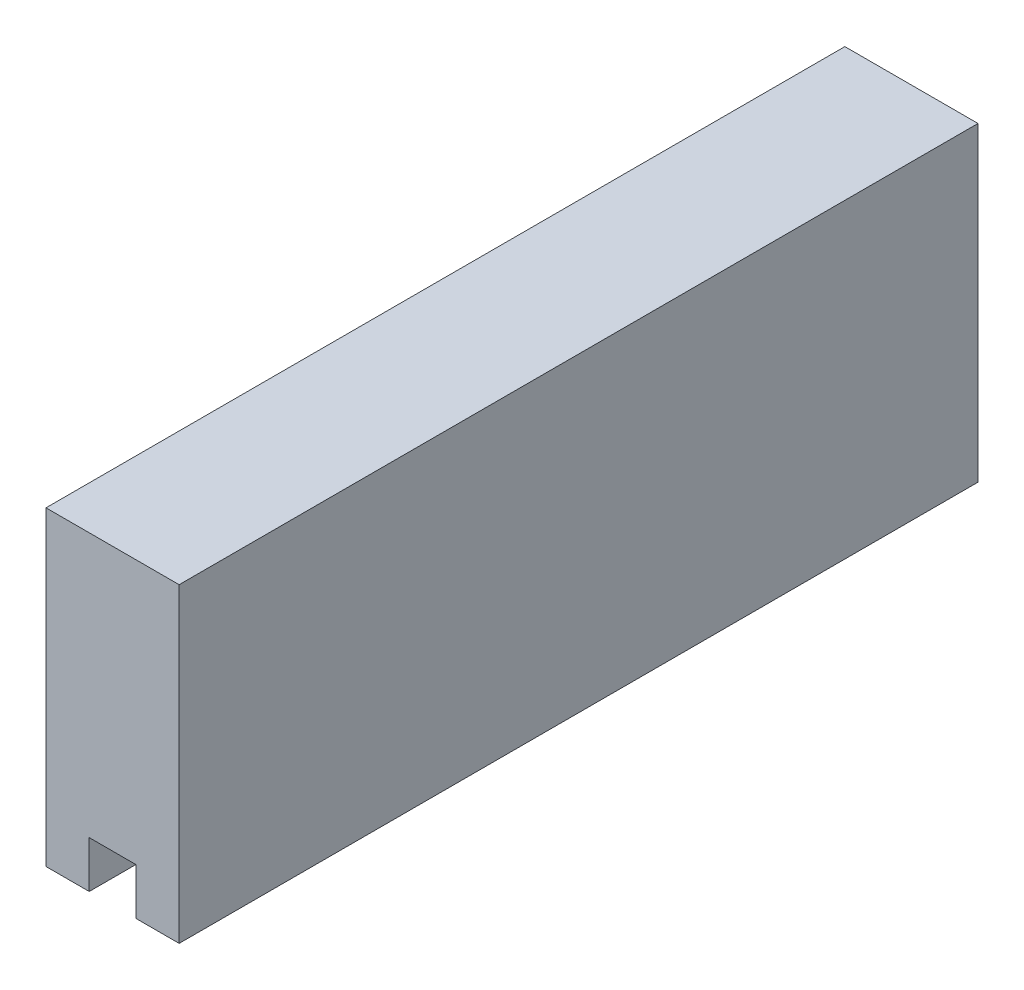
SolidWorks part; units mm, degrees
ref_plane "xy_plane" through (0, 0, 0) normal (0, 0, 1) x (1, 0, 0)
ref_plane "zx_plane" through (0, 0, 0) normal (0, 1, 0) x (1, 0, 0)
ref_plane "yz_plane" through (0, 0, 0) normal (1, 0, 0) x (0, 0, -1)
ref_axis "x_axis" through (-80.9, 0, 0) along (1, 0, 0)
ref_axis "y_axis" through (0, -50, 0) along (0, 1, 0)
ref_axis "z_axis" through (0, 0, -80.9) along (0, 0, 1)
ref_plane "xMid_plane" through (0, 0, 0) normal (1, 0, 0) x (0, 0, -1)
ref_plane "xMin_plane" through (-15, 0, 0) normal (1, 0, 0) x (0, 0, -1)
ref_plane "xMax_plane" through (15, 0, 0) normal (1, 0, 0) x (0, 0, -1)
ref_plane "yMid_plane" through (0, 0, 0) normal (0, 1, 0) x (1, 0, 0)
ref_plane "yMin_plane" through (0, -35, 0) normal (0, 1, 0) x (1, 0, 0)
ref_plane "yMax_plane" through (0, 35, 0) normal (0, 1, 0) x (1, 0, 0)
ref_plane "zMid_plane" through (0, 0, 0) normal (0, 0, 1) x (1, 0, 0)
ref_plane "zMin_plane" through (0, 0, -90) normal (0, 0, 1) x (1, 0, 0)
ref_plane "zMax_plane" through (0, 0, 90) normal (0, 0, 1) x (1, 0, 0)
sketch "projectionXy_sketch" plane through (0, 0, 0) normal (0, 0, 1) x (1, 0, 0)
  line L0 (55, 35) -> (-55, 35) construction
  line L1 (-15, 35) -> (15, 35)
  line L2 (-15, 35) -> (-15, -35)
  line L3 (-15, -35) -> (15, -35)
  line L4 (15, 35) -> (15, -35)
  line L5 (55, -35) -> (-55, -35) construction
  line L6 (15, -55) -> (15, 55) construction
  line L7 (-15, -55) -> (-15, 55) construction
extrude "mainBody_extrude" add sketch "projectionXy_sketch" along normal up to surface (90 mm away) from surface up to plane "zMax_plane" starting at plane "zMin_plane"
sketch "trough_sketch" plane through (0, 0, 0) normal (0, 0, -1) x (1, 0, 0)
  line L0 (0, -55) -> (0, 55) construction
  line L1 (-5.2573, 24.4854) -> (5.2573, 24.4854)
  line L2 (-5.2573, 24.4854) -> (-5.2573, 35)
  line L3 (-5.2573, 35) -> (5.2573, 35)
  line L4 (5.2573, 24.4854) -> (5.2573, 35)
  line L6 (-55, 35) -> (55, 35) construction
  point P4 (0, 35)
  dimension "D1" = 10.5146
  dimension "D2" = 10.5146
extrude "trough_cut" cut sketch "trough_sketch" against normal through all both and the other way through all from surface starting at plane "zMid_plane"
equation "\"D1@xMin_plane\"= \"externalParameters.this.extentX\" / 2"
equation "\"D1@xMax_plane\" = \"externalParameters.this.extentX\" / 2"
equation "\"D1@yMin_plane\" = \"externalParameters.this.extentY\" / 2"
equation "\"D1@yMax_plane\" = \"externalParameters.this.extentY\" / 2"
equation "\"D1@zMin_plane\" = \"externalParameters.this.extentZ\" / 2"
equation "\"D1@zMax_plane\" = \"externalParameters.this.extentZ\" / 2"
equation "\"D1@trough_sketch\"=\"externalParameters.this.trough.extentX\""
equation "\"D2@trough_sketch\"=\"externalParameters.this.trough.extentY\""
